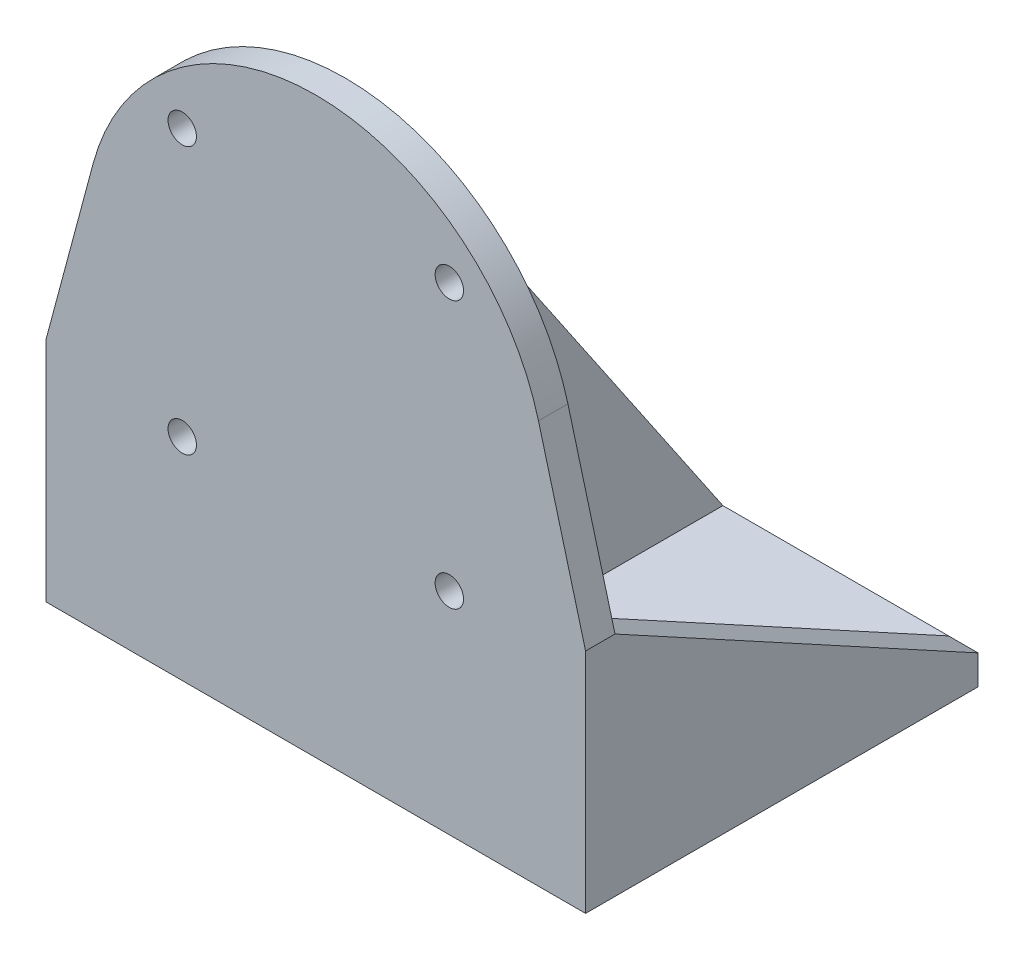
SolidWorks part; units mm, degrees
ref_plane "前视基准面" through (0, 0, 0) normal (0, 0, 1) x (1, 0, 0)
ref_plane "上视基准面" through (0, 0, 0) normal (0, 1, 0) x (1, 0, 0)
ref_plane "右视基准面" through (0, 0, 0) normal (1, 0, 0) x (0, 0, -1)
other "Configuration Table"
sketch "草图1" plane through (0, 0, 0) normal (0, 0, 1) x (1, 0, 0)
  line L0 (0, 0) -> (0, -7.9871) construction
  line L1 (0, -27.224) -> (27.224, -27.224) construction
  line L2 (27.224, 0) -> (27.224, -27.488) construction
  line L3 (-13.888, -25.5783) -> (-13.888, -48.744)
  line L4 (13.612, -13.744) -> (13.612, 6.8594) construction
  line L5 (36.3113, -7.6617) -> (41.112, -25.5783)
  line L6 (-9.0873, -7.6617) -> (-13.888, -25.5783)
  line L7 (41.112, -25.5783) -> (41.112, -48.744)
  line L8 (-13.888, -48.744) -> (41.112, -48.744)
  circle A0 centre (0, 0) radius 1.4478
  circle A1 centre (27.224, 0) radius 1.4478
  circle A2 centre (0, -27.224) radius 1.4478
  circle A3 centre (27.224, -27.224) radius 1.4478
  arc A4 (-9.0873, -7.6617) -> (36.3113, -7.6617) centre (13.612, -13.744) cw
  dimension "D1" = 2.8955
  dimension "D3" = 27.224
  dimension "D5" = 27.224
  dimension "D6" = 23.5
  dimension "D7" = 18.5486
  dimension "D8" = 23.1656
  dimension "D2" = 2
  dimension "D4" = 2
extrude "凸台-拉伸1" add sketch "草图1" against normal blind 3
sketch "草图2" plane through (0, 0, -3) normal (0, 0, -1) x (-1, 0, 0)
  line L0 (-41.112, -45.744) -> (13.888, -45.744)
  line L1 (-41.112, -48.744) -> (-41.112, -25.5783) construction
  line L2 (13.888, -25.5783) -> (13.888, -48.744) construction
  line L3 (13.888, -48.744) -> (-41.112, -48.744) construction
  line L9 (-36.3113, -7.6617) -> (-41.112, -25.5783)
  line L10 (-41.112, -25.5783) -> (-41.112, -48.744)
  line L11 (-41.112, -48.744) -> (13.888, -48.744)
  line L12 (13.888, -48.744) -> (13.888, -25.5783)
  line L13 (13.888, -25.5783) -> (9.0873, -7.6617)
  line L15 (-41.112, -45.744) -> (-41.112, -48.744)
  line L16 (-41.112, -48.744) -> (13.888, -48.744)
  line L17 (13.888, -48.744) -> (13.888, -45.744)
  arc A1 (9.0873, -7.6617) -> (-36.3113, -7.6617) centre (-13.612, -13.744) ccw
  dimension "D1" = 3
  dimension "D2" = 0
extrude "凸台-拉伸2" add sketch "草图2" along normal blind 37
sketch "草图3" plane through (0, -45.744, 0) normal (0, 1, 0) x (1, 0, 0)
  line L0 (13.612, 40) -> (13.612, 3) construction
  line L2 (-13.888, 40) -> (41.112, 40) construction
  line L3 (36.3113, 3) -> (-9.0873, 3) construction
  line L4 (32.312, 13) -> (32.312, 30)
  line L5 (41.112, 40) -> (41.112, 3) construction
  line L6 (-13.888, 21.5) -> (41.112, 21.5) construction
  line L7 (-13.888, 40) -> (-13.888, 3) construction
  line L8 (32.312, 30) -> (30.712, 30) construction
  line L9 (29.112, 30) -> (29.112, 13)
  line L10 (-1.888, 30) -> (-1.888, 13)
  line L11 (-5.088, 13) -> (-5.088, 30)
  arc A0 (32.312, 30) -> (29.112, 30) centre (30.712, 30) ccw
  arc A1 (32.312, 13) -> (29.112, 13) centre (30.712, 15.7693) cw
  arc A2 (-5.088, 13) -> (-1.888, 13) centre (-3.488, 15.7693) ccw
  arc A3 (-5.088, 30) -> (-1.888, 30) centre (-3.488, 30) cw
  point P8 (32.312, 21.5)
  dimension "D1" = 8.8
  dimension "D2" = 1.6
extrude "切除-拉伸1" cut sketch "草图3" against normal blind 3
ref_plane "基准面1" through (41.112, 0, 0) normal (1, 0, 0) x (0, 0, -1)
sketch "草图4" plane through (41.112, 0, 0) normal (1, 0, 0) x (0, 0, -1)
  line L0 (40, -45.744) -> (3, -25.5783)
  line L1 (3, -45.744) -> (3, -25.5783) construction
  line L2 (3, -25.5783) -> (3, -7.6617) construction
  line L3 (3, -25.5783) -> (3, -45.744)
  line L4 (3, -45.744) -> (40, -45.744)
  dimension "D1" = 42.1385
extrude "凸台-拉伸3" add sketch "草图4" against normal blind 3
ref_plane "基准面2" through (13.612, 0, 0) normal (-1, 0, 0) x (0, 1, 0)
sketch "草图12" plane through (0, 0, -3) normal (0, 0, -1) x (-1, 0, 0)
  line L0 (-13.612, -13.744) -> (-13.612, 13.9999) construction
  line L1 (-13.612, -30.25) -> (-13.612, 30.25) construction
  line L2 (-13.612, 13.9999) -> (-13.612, -53.4393) construction
sketch "草图10" plane through (13.612, 0, 0) normal (-1, 0, 0) x (0, 1, 0)
  line L1 (-45.744, 40) -> (-45.744, 3) construction
  line L2 (-45.744, 40) -> (-25.5783, 3) construction
  line L4 (-45.744, 40) -> (-45.744, 3)
sketch "草图13" plane through (13.612, 0, 0) normal (-1, 0, 0) x (0, 1, 0)
  line L0 (-45.744, 40) -> (8.756, 3)
  line L1 (13.9999, 3) -> (-53.4393, 3) construction
  line L2 (-45.744, 40) -> (-45.744, 3)
  line L3 (-45.744, 3) -> (8.756, 3)
  dimension "D1" = 65.873
extrude "凸台-拉伸4" add sketch "草图13" along normal blind 1.5 and the other way blind 1.5
mirror "镜向1" about plane through (13.612, 0, 0) normal (-1, 0, 0) of "凸台-拉伸3"
